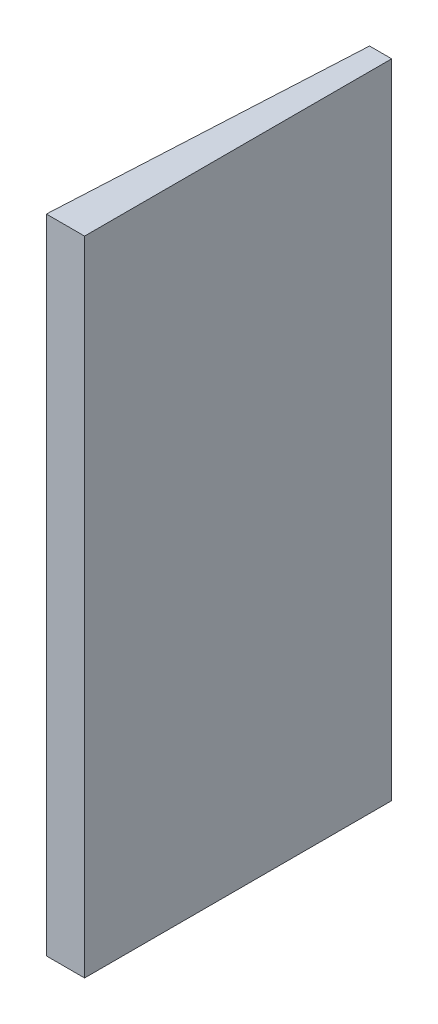
SolidWorks part; units mm, degrees
ref_plane "Top Plane" through (0, 0, 0) normal (0, 0, 1) x (1, 0, 0)
ref_plane "Front Plane" through (0, 0, 0) normal (0, 1, 0) x (1, 0, 0)
ref_plane "Right Plane" through (0, 0, 0) normal (1, 0, 0) x (0, 0, -1)
sketch "Sketch1" plane through (0, 0, 0) normal (0, 1, 0) x (1, 0, 0)
  line L0 (0, 20.0577) -> (0, -20.0923)
  line L1 (0, -20.0923) -> (-5, -20.0923)
  line L2 (-5, -20.0923) -> (-2.8958, 20.0577)
  line L3 (-2.8958, 20.0577) -> (0, 20.0577)
  dimension "D1" = 93
  dimension "D2" = 5
  dimension "D3" = 40.15
  dimension "D4" = 20.0923
extrude "Boss-Extrude1" add sketch "Sketch1" along normal mid plane 84
sketch "Sketch2" plane through (-3.9362, 0, -0.2063) normal (-0.9986, 0, -0.0523) x (-0.0523, 0, 0.9986)
  circle A0 centre (-4.6235, -29.8957) radius 6.3 construction
  circle A1 centre (-4.6235, 29.8957) radius 6.3 construction
  circle A2 centre (-4.6235, -29.8957) radius 6.3
  circle A3 centre (-4.6235, 29.8957) radius 6.3
ref_plane "Plane1" through (-6.9321, 0, -0.3633) normal (-0.9986, 0, -0.0523) x (-0.0523, 0, 0.9986)
sketch "Sketch3" plane through (-6.9321, 0, -0.3633) normal (-0.9986, 0, -0.0523) x (-0.0523, 0, 0.9986)
  circle A0 centre (-4.6235, -29.8957) radius 3.3
  circle A1 centre (-4.6235, 29.8957) radius 3.3
  point P0 (-4.6235, 29.8957)
  point P2 (-4.6235, -29.8957)
  dimension "D1" = 6.6
  dimension "D2" = 6.6
loft "Loft2" add section "Sketch3" section "Sketch2" connector at (-6.7449, -26.7663, -3.9346) connector at (-3.874, -24.6149, -1.3925)
loft "Loft3" add section "Sketch3<7>" section "Sketch2<6>" connector at (-6.734, 33.0873, -4.1429) connector at (-3.7945, 35.897, -2.9094)
sketch "Sketch3<7>" plane through (-6.9321, 0, -0.3633) normal (-0.9986, 0, -0.0523) x (-0.0523, 0, 0.9986) same geometry as "Sketch3"
sketch "Sketch2<6>" plane through (-3.9362, 0, -0.2063) normal (-0.9986, 0, -0.0523) x (-0.0523, 0, 0.9986) same geometry as "Sketch2"
